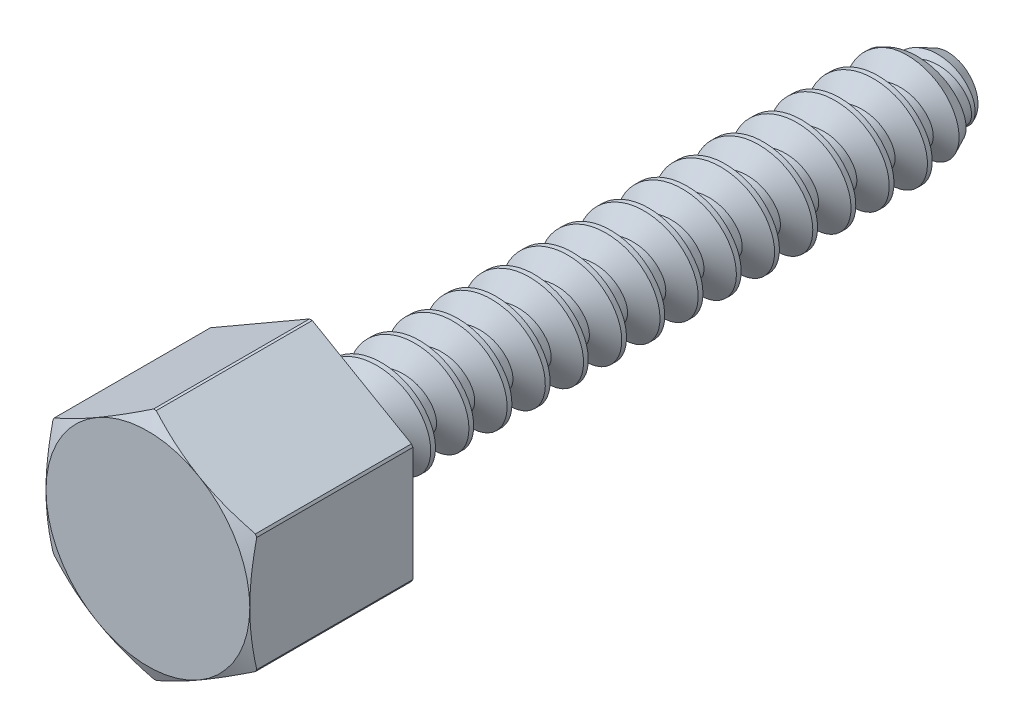
SolidWorks part; units mm, degrees
material "AISI 304"
ref_plane "Front" through (0, 0, 0) normal (0, 0, 1) x (1, 0, 0)
ref_plane "Top" through (0, 0, 0) normal (0, 1, 0) x (1, 0, 0)
ref_plane "Right" through (0, 0, 0) normal (1, 0, 0) x (0, 0, -1)
sketch "Sketch1" plane through (0, 0, 0) normal (1, 0, 0) x (0, 0, -1)
  line L0 (0, 0) -> (-6.4, 0) construction
  line L1 (0, 0) -> (25, 0)
  line L2 (0, 0) -> (0, 2)
  line L3 (0, 2) -> (25, 2)
  line L4 (25, 0) -> (25, 2)
  line L5 (0, -2) -> (25, -2) construction
  point P7 (17.4062, 2)
  point P8 (17.4062, -2)
  dimension "D1" = 25
  dimension "Length" = 25
revolve "Revolve1" add sketch "Sketch1" angle 360 about L0
sketch "Sketch6" plane through (0, 0, -25) normal (0, 0, -1) x (-1, 0, 0)
  circle A0 centre (0, 0) radius 2 construction
  circle A1 centre (0, 0) radius 2
curve "Helix/Spiral1" pitch 1.5 height 30 radius 2 centre (0, 0, -25) axis (0, 0, 1) start towards (0, 1, 0) parameters "Lenght"=30, "Pitch"=1.5
sketch "Sketch2" plane through (0, 0, 0) normal (1, 0, 0) x (0, 0, -1)
  line L1 (24.9062, 2.1624) -> (25.6563, 0.8633) construction
  line L2 (25.6563, 0.8633) -> (26.4063, 2.1624) construction
  line L3 (26.4063, 2.1624) -> (24.9062, 2.1624) construction
  line L4 (25.6563, 2.1624) -> (25.6563, 0.8633) construction
  line L5 (25, 2) -> (26.3125, 2) construction
  line L6 (26.3125, 2) -> (25.8438, 1.1881)
  line L7 (25.8438, 1.1881) -> (25.4688, 1.1881)
  line L8 (26.3125, 2) -> (24.9062, 2.1624)
  line L9 (24.9062, 2.1624) -> (25.4688, 1.1881)
  dimension "D2" = 0.375
  dimension "D3" = 1.3125
  dimension "D1" = 60
sweep "Cut-Sweep1" cut profiles "Sketch2" path "Helix/Spiral1" align with end faces yes
sketch "Sketch3" plane through (0, 0, 0) normal (1, 0, 0) x (0, 0, -1)
  line L0 (25, 1.1881) -> (23.2589, 2)
  line L1 (23.2589, 2) -> (25, 2)
  line L2 (25, 2) -> (25, 1.1881)
  line L3 (0, 2) -> (25, 2) construction
  line L4 (25, 0) -> (25, 2) construction
  line L5 (23.2589, 0) -> (0, 0) construction
  line L6 (23.2589, 2) -> (23.2589, -2) construction
  line L7 (0, -2) -> (25, -2) construction
  line L8 (25, 1.4142) -> (25, 2) construction
  line L9 (25, 1.1881) -> (25.4688, 1.1881) construction
  dimension "D1" = 25
  dimension "D2" = 4
revolve "Cut-Revolve2" cut sketch "Sketch3" angle 360 about L5
sketch "Sketch4" plane through (0, 0, 0) normal (0, 0, 1) x (1, 0, 0)
  line L1 (0, 4.6188) -> (-4, 2.3094)
  line L2 (-4, 2.3094) -> (-4, -2.3094)
  line L3 (-4, -2.3094) -> (0, -4.6188)
  line L4 (0, -4.6188) -> (4, -2.3094)
  line L5 (4, -2.3094) -> (4, 2.3094)
  line L6 (4, 2.3094) -> (0, 4.6188)
  circle A0 centre (0, 0) radius 4 construction
  circle A1 centre (0, 0) radius 4 construction
  dimension "Head Dia" = 8
extrude "Extrude1" add sketch "Sketch4" along normal up to vertex (6.4 mm away) up to point (0, 0, 6.4)
sketch "Sketch5" plane through (0, 0, 0) normal (1, 0, 0) x (0, 0, -1)
  line L0 (-6.4, 4) -> (-6.1259, 4.5879)
  line L1 (0, 4.6188) -> (-6.4, 4.6188)
  line L2 (-6.4, 4.6188) -> (-6.4, 4)
  line L3 (0, 0) -> (-6.4, 0) construction
  line L4 (-6.4, 4.6188) -> (0, 4.6188) construction
  line L5 (-6.4, 2.3094) -> (-6.4, 4.6188) construction
  line L6 (-6.1259, 4.5879) -> (0, 4.5879)
  line L7 (-6.4, 4) -> (0, 4) construction
  line L10 (0, 4.5879) -> (0, 4.6188)
  line L11 (0, 2.3094) -> (0, 4.6188) construction
  dimension "D1" = 25
  dimension "D3" = 0.6188
  dimension "D4" = 0.0309
  dimension "D5" = 6.4
  dimension "D6" = 25
revolve "Cut-Revolve3" cut sketch "Sketch5" angle 360 about L3
equation "\"D2@Sketch2\"=\"Thread Pitch@Sketch2\"*1/4"
equation "\"D3@Sketch2\"=\"Thread Pitch@Sketch2\"*7/8"
equation "\"D4@Sketch5\"=\"D3@Sketch5\"/20"
equation "\"Pitch@Helix/Spiral1\" = \"Thread Pitch@Sketch2\""
equation "\"Lenght@Helix/Spiral1\" = 30"
equation "\"Note Dim@Sketch1\" = \"Thread Pitch@Sketch2\"*5.0625"
